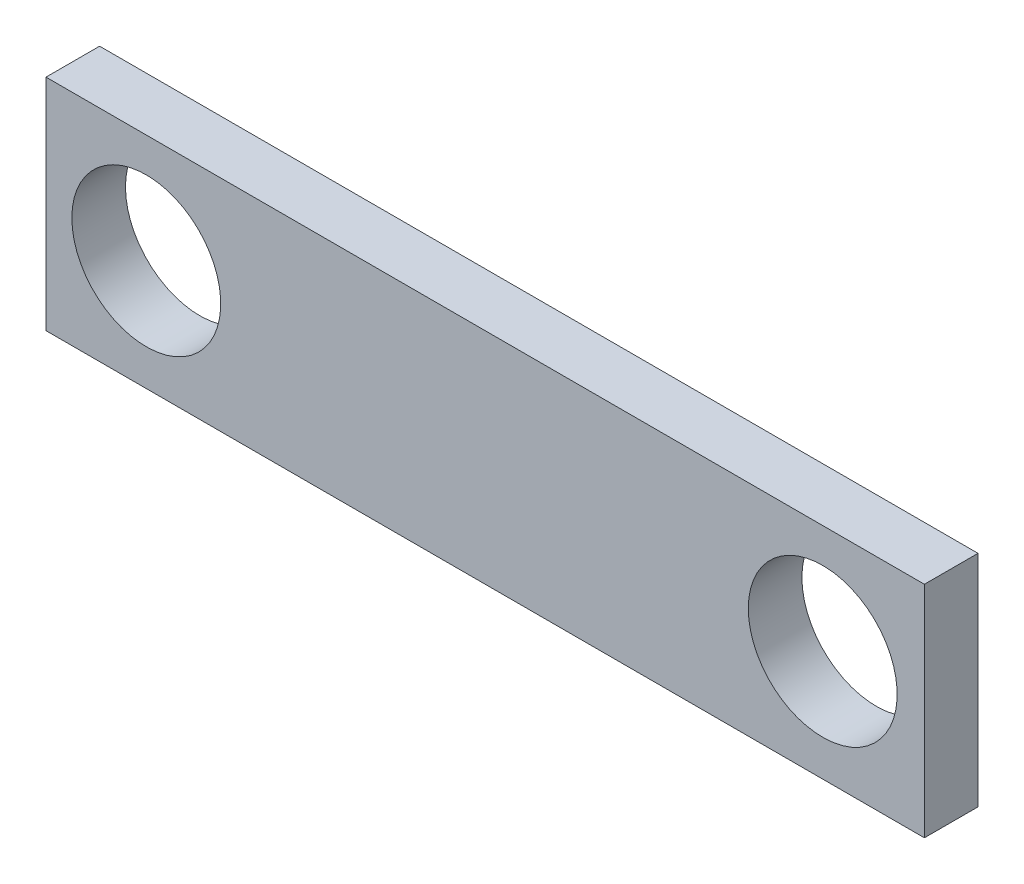
SolidWorks part; units mm, degrees
ref_plane "Plan de face" through (0, 0, 0) normal (0, 0, 1) x (1, 0, 0)
ref_plane "Plan de dessus" through (0, 0, 0) normal (0, 1, 0) x (1, 0, 0)
ref_plane "Plan de droite" through (0, 0, 0) normal (1, 0, 0) x (0, 0, -1)
sketch "Esquisse2" plane through (0, 0, 3) normal (0, 0, 1) x (1, 0, 0)
  line L1 (1.2382, -53.7991) -> (26.6382, -53.7991)
  line L2 (1.2382, -53.7991) -> (1.2382, -60.1491)
  line L3 (1.2382, -60.1491) -> (26.6382, -60.1491)
  line L4 (26.6382, -53.7991) -> (26.6382, -60.1491)
  point P7 (0, 0)
  dimension "D1" = 25.4
  dimension "D2" = 6.35
extrude "Boss.-Extru.1" add sketch "Esquisse2" along normal blind 1.55 contours L3 L4 L1 L2
hole_wizard "Dégagement #61" positions "Esquisse3" profile "Esquisse4" hole size "#6" standard "Ansi Inch" end condition through all
sketch "Esquisse3" plane through (0, 0, 3) normal (0, 0, -1) x (-1, 0, 0)
  line L0 (-1.2382, -53.7991) -> (-1.2382, -60.1491) construction
  line L1 (-1.2382, -60.1491) -> (-26.6382, -60.1491) construction
  point P0 (-4.1382, -56.9491)
  point P2 (-23.6982, -56.9491)
  dimension "D1" = 19.56
  dimension "D2" = 2.9
  dimension "D3" = 3.2
  dimension "D4" = 3.2
sketch "Esquisse4" plane through (4.1382, -56.9491, 3) normal (1, 0, 0) x (0, 1, 0)
  line L0 (0, 0) -> (0, 1.55)
  line L1 (0, 1.55) -> (2.1526, 1.55)
  line L2 (2.1526, 1.55) -> (2.1526, 0)
  line L5 (2.1526, 0) -> (0, 0)
  line L11 (0, -6.35) -> (0, 107.95) construction
  dimension "Diamètre du perçage jusqu'au prochain" = 4.3053
  dimension "Profondeur du perçage jusqu'au prochain" = 1.55
